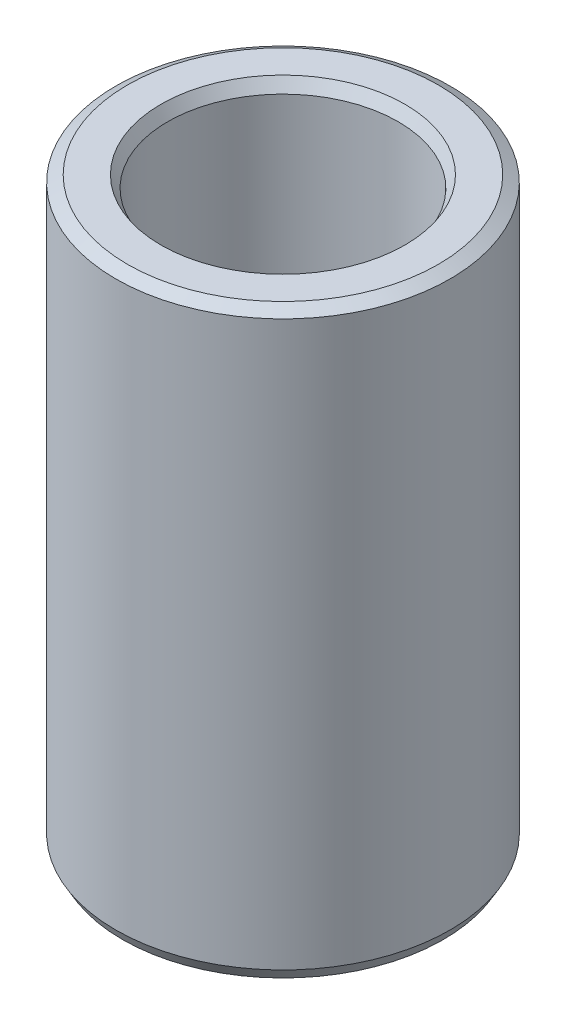
SolidWorks part; units mm, degrees
ref_plane "Front Plane" through (0, 0, 0) normal (0, 0, 1) x (1, 0, 0)
ref_plane "Top Plane" through (0, 0, 0) normal (0, 1, 0) x (1, 0, 0)
ref_plane "Right Plane" through (0, 0, 0) normal (1, 0, 0) x (0, 0, -1)
sketch "Sketch1" plane through (0, 0, 0) normal (0, 1, 0) x (1, 0, 0)
  circle A0 centre (0, 0) radius 37.5
  dimension "SLEEVE_OD" = 75
extrude "Boss-Extrude1" add sketch "Sketch1" along normal blind 130.6583
sketch "Sketch2" plane through (0, 0, 0) normal (0, 1, 0) x (1, 0, 0)
  circle A0 centre (0, 0) radius 25.8552
  dimension "BORE_D" = 51.7105
extrude "Cut-Extrude1" cut sketch "Sketch2" along normal through all
chamfer "Chamfer1" distance 1.5181 angle 60 4 edges at (0, 130.6583, 25.8552) (0, 0, 25.8552) (0, 0, 37.5) (0, 130.6583, 37.5) first distance on face at (0, 130.6583, 25.8552) first distance on face at (0, 0, 25.8552) first distance on face at (0, 130.6583, 37.5)
